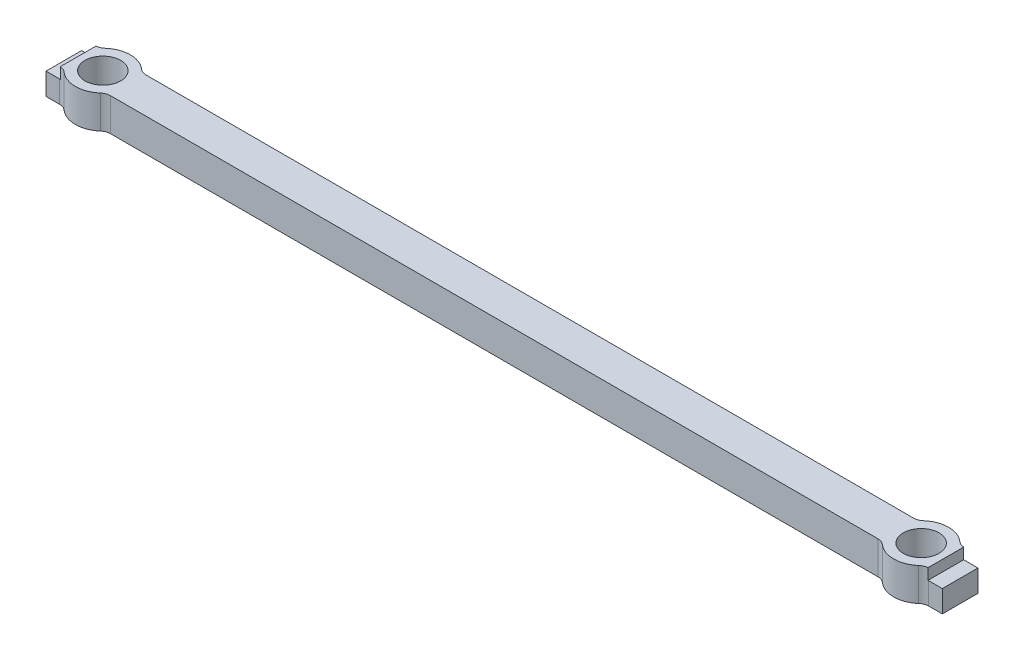
SolidWorks part; units mm, degrees
ref_plane "Front Plane" through (0, 0, 0) normal (0, 0, 1) x (1, 0, 0)
ref_plane "Top Plane" through (0, 0, 0) normal (0, 1, 0) x (1, 0, 0)
ref_plane "Right Plane" through (0, 0, 0) normal (1, 0, 0) x (0, 0, -1)
sketch "Sketch1" plane through (0, 0, 0) normal (0, 1, 0) x (1, 0, 0)
  line L0 (-39.5, 2.5) -> (-39.5, -2.5) construction
  line L1 (-40.8, 2.5) -> (40.8, 2.5)
  line L2 (-40.8, 2.5) -> (-40.8, -2.5)
  line L3 (-40.8, -2.5) -> (40.8, -2.5)
  line L4 (40.8, 2.5) -> (40.8, -2.5)
  line L5 (-40.8, 2.5) -> (40.8, -2.5) construction
  line L6 (-40.8, -2.5) -> (40.8, 2.5) construction
  line L7 (-37.25, 2.5) -> (-37.25, -2.5) construction
  line L8 (-40.8, 0) -> (40.8, 0) construction
  line L9 (0, 2.5) -> (0, -2.5) construction
  line L11 (40.8, 1.625) -> (-40.8, 1.625)
  line L12 (40.8, 1.625) -> (40.8, -1.625)
  line L13 (40.8, -1.625) -> (-40.8, -1.625)
  line L14 (-40.8, 1.625) -> (-40.8, -1.625)
  line L15 (40.8, 1.625) -> (-40.8, -1.625) construction
  line L16 (40.8, -1.625) -> (-40.8, 1.625) construction
  circle A0 centre (-37.25, 0) radius 1.625
  circle A1 centre (-37.25, 0) radius 2.5
  circle A2 centre (37.25, 0) radius 1.625
  circle A3 centre (37.25, 0) radius 2.5
  point P0 (0, 0)
  point P17 (0, 0)
  dimension "D5" = 3.25
  dimension "D1" = 81.6
  dimension "D2" = 5
  dimension "D3" = 1.3
  dimension "D4" = 2.25
extrude "Shape" add sketch "Sketch1" along normal blind 3 contours L11 A3 L13 L4 | A3 L11 A2 L13 | A3 L13 | A3 L11 | A3 L13 A2 L11 | L13 A3 L11 A1 | L13 A1 L11 A0 | L11 A1 | L11 A1 L13 A0 | A1 L13 | A1 L11 L2 L13 region at (-37.25, 0, -1.9808) region at (-40.168, 0, 0) region at (37.25, 0, -1.9808) region at (-35.5053, 0, 0) region at (0, 0, 0) region at (-38.9947, 0, 0) region at (38.9947, 0, 0) region at (40.168, 0, 0) region at (35.5053, 0, 0) region at (-37.25, 0, 1.9808) region at (37.25, 0, 1.9808)
fillet "Mill fillets" radius 1 8 edges at (39.1498, 1.5, -1.625) (-35.3502, 1.5, -1.625) (-39.1498, 1.5, -1.625) (35.3502, 1.5, -1.625) (-39.1498, 1.5, 1.625) (35.3502, 1.5, 1.625) (39.1498, 1.5, 1.625) (-35.3502, 1.5, 1.625)
sketch "Sketch2" plane through (0, 3, 0) normal (0, 1, 0) x (1, 0, 0)
  line L0 (-39.5, 1.6271) -> (-39.5, -1.6271)
  line L1 (0, 1.625) -> (0, -1.625) construction
  line L2 (39.5, 1.6271) -> (39.5, -1.6271)
  line L8 (34.935, 1.625) -> (-34.935, 1.625)
  line L9 (-39.565, 1.625) -> (-40.8, 1.625)
  line L10 (-40.8, 1.625) -> (-40.8, -1.625)
  line L11 (-40.8, -1.625) -> (-39.565, -1.625)
  line L12 (-34.935, -1.625) -> (34.935, -1.625)
  line L13 (39.565, -1.625) -> (40.8, -1.625)
  line L14 (40.8, -1.625) -> (40.8, 1.625)
  line L15 (40.8, 1.625) -> (39.565, 1.625)
  line L16 (34.935, 1.625) -> (-34.935, 1.625)
  line L17 (-39.565, 1.625) -> (-40.8, 1.625)
  line L18 (-40.8, 1.625) -> (-40.8, -1.625)
  line L19 (-40.8, -1.625) -> (-39.565, -1.625)
  line L20 (-34.935, -1.625) -> (34.935, -1.625)
  line L21 (39.565, -1.625) -> (40.8, -1.625)
  line L22 (40.8, -1.625) -> (40.8, 1.625)
  line L23 (40.8, 1.625) -> (39.565, 1.625)
  arc A12 (-35.5964, 1.875) -> (-34.935, 1.625) centre (-34.935, 2.625) ccw
  arc A13 (-35.5964, 1.875) -> (-38.9036, 1.875) centre (-37.25, 0) ccw
  arc A14 (-39.565, 1.625) -> (-38.9036, 1.875) centre (-39.565, 2.625) ccw
  arc A15 (-38.9036, -1.875) -> (-39.565, -1.625) centre (-39.565, -2.625) ccw
  arc A16 (-38.9036, -1.875) -> (-35.5964, -1.875) centre (-37.25, 0) ccw
  arc A17 (-34.935, -1.625) -> (-35.5964, -1.875) centre (-34.935, -2.625) ccw
  arc A18 (35.5964, -1.875) -> (34.935, -1.625) centre (34.935, -2.625) ccw
  arc A19 (35.5964, -1.875) -> (38.9036, -1.875) centre (37.25, 0) ccw
  arc A20 (39.565, -1.625) -> (38.9036, -1.875) centre (39.565, -2.625) ccw
  arc A21 (38.9036, 1.875) -> (39.565, 1.625) centre (39.565, 2.625) ccw
  arc A22 (38.9036, 1.875) -> (35.5964, 1.875) centre (37.25, 0) ccw
  arc A23 (34.935, 1.625) -> (35.5964, 1.875) centre (34.935, 2.625) ccw
  arc A24 (-35.5964, 1.875) -> (-34.935, 1.625) centre (-34.935, 2.625) ccw
  arc A25 (-35.5964, 1.875) -> (-38.9036, 1.875) centre (-37.25, 0) ccw
  arc A26 (-39.565, 1.625) -> (-38.9036, 1.875) centre (-39.565, 2.625) ccw
  arc A27 (-38.9036, -1.875) -> (-39.565, -1.625) centre (-39.565, -2.625) ccw
  arc A28 (-38.9036, -1.875) -> (-35.5964, -1.875) centre (-37.25, 0) ccw
  arc A29 (-34.935, -1.625) -> (-35.5964, -1.875) centre (-34.935, -2.625) ccw
  arc A30 (35.5964, -1.875) -> (34.935, -1.625) centre (34.935, -2.625) ccw
  arc A31 (35.5964, -1.875) -> (38.9036, -1.875) centre (37.25, 0) ccw
  arc A32 (39.565, -1.625) -> (38.9036, -1.875) centre (39.565, -2.625) ccw
  arc A33 (38.9036, 1.875) -> (39.565, 1.625) centre (39.565, 2.625) ccw
  arc A34 (38.9036, 1.875) -> (35.5964, 1.875) centre (37.25, 0) ccw
  arc A35 (34.935, 1.625) -> (35.5964, 1.875) centre (34.935, 2.625) ccw
  arc M26 (-38.9036, 1.875) -> (-39.565, 1.625) centre (-39.565, 2.625) cw
  line M27 (-39.565, 1.625) -> (-40.8, 1.625)
  line M28 (-40.8, 1.625) -> (-40.8, -1.625)
  line M29 (-40.8, -1.625) -> (-39.565, -1.625)
  arc M30 (-39.565, -1.625) -> (-38.9036, -1.875) centre (-39.565, -2.625) cw
  arc M36 (38.9036, -1.875) -> (39.565, -1.625) centre (39.565, -2.625) cw
  line M37 (39.565, -1.625) -> (40.8, -1.625)
  line M38 (40.8, -1.625) -> (40.8, 1.625)
  line M39 (40.8, 1.625) -> (39.565, 1.625)
  arc M40 (39.565, 1.625) -> (38.9036, 1.875) centre (39.565, 2.625) cw
  dimension "D2" = 1.3
  dimension "D1" = 0
extrude "Edge cuts" cut sketch "Sketch2" against normal offset from surface (1 mm away) 2 contours L0 M26 M27 M28 M29 M30 | L2 M40 M36 M37 M38 M39 region at (-40.15, 3, 0) region at (40.15, 3, 0) up to face at (0, 0, 0)
